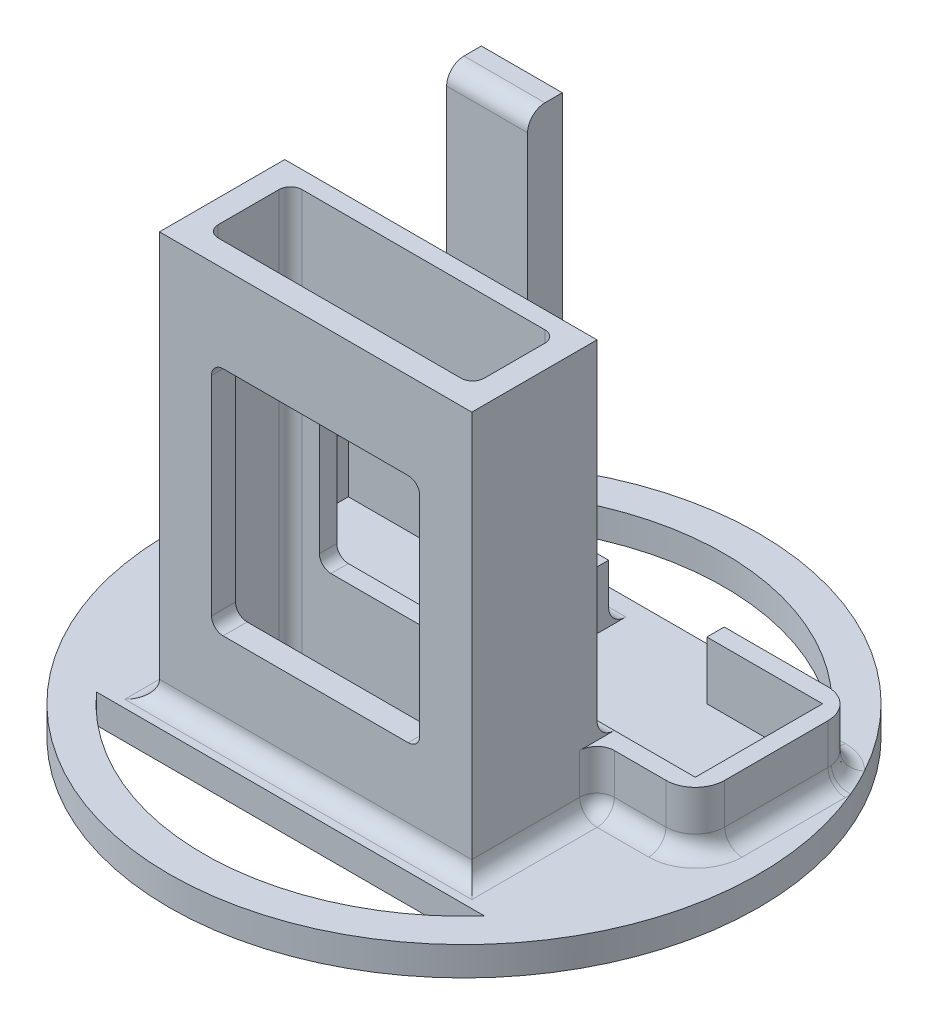
SolidWorks part; units mm, degrees
ref_plane "Front Plane" through (0, 0, 0) normal (0, 0, 1) x (1, 0, 0)
ref_plane "Top Plane" through (0, 0, 0) normal (0, 1, 0) x (1, 0, 0)
ref_plane "Right Plane" through (0, 0, 0) normal (1, 0, 0) x (0, 0, -1)
sketch "Sketch1" plane through (0, 0, 0) normal (0, 1, 0) x (1, 0, 0)
  line L1 (-16.7705, 15) -> (16.7705, 15)
  line L2 (-16.7705, 15) -> (-16.7705, -15)
  line L3 (-16.7705, -15) -> (16.7705, -15)
  line L4 (16.7705, 15) -> (16.7705, -15)
  line L5 (-16.7705, 15) -> (16.7705, -15) construction
  line L6 (-16.7705, -15) -> (16.7705, 15) construction
  circle A0 centre (0, 0) radius 25.5
  circle A1 centre (0, 0) radius 22.5
  dimension "D1" = 51
  dimension "D2" = 45
  dimension "D3" = 30
extrude "Boss-Extrude1" add sketch "Sketch1" along normal blind 2.5 contours L2 A1 | L4 A1 | L4 L1 L2 L3 | A0 A1 region at (0, 0, 0) region at (-19.0893, 0, 0) region at (19.0893, 0, 0) region at (-24.7788, 0, 0)
sketch "Sketch2" plane through (0, 2.5, 0) normal (0, 1, 0) x (1, 0, 0)
  line L1 (-20.5, 5.5) -> (20.5, 5.5)
  line L2 (-20.5, 5.5) -> (-20.5, -5.5)
  line L3 (-20.5, -5.5) -> (20.5, -5.5)
  line L4 (20.5, 5.5) -> (20.5, -5.5)
  line L5 (-20.5, 5.5) -> (20.5, -5.5) construction
  line L6 (-20.5, -5.5) -> (20.5, 5.5) construction
  line L7 (-20.5, -0.5) -> (20.5, -0.5)
  line L8 (-20.5, -0.5) -> (-20.5, 10.5)
  line L9 (-20.5, 10.5) -> (20.5, 10.5)
  line L10 (20.5, -0.5) -> (20.5, 10.5)
  line L11 (-20.5, -0.5) -> (-22, -0.5)
  line L12 (-20.5, -0.5) -> (-20.5, 10.5)
  line L13 (-20.5, 10.5) -> (-22, 10.5)
  line L14 (-22, -0.5) -> (-22, 10.5)
  line L15 (-22, -0.5) -> (20.5, -0.5)
  line L16 (-22, -0.5) -> (-22, -2)
  line L17 (-22, -2) -> (20.5, -2)
  line L18 (20.5, -0.5) -> (20.5, -2)
  line L19 (-22, 10.5) -> (20.5, 10.5)
  line L20 (-22, 10.5) -> (-22, 12)
  line L21 (-22, 12) -> (20.5, 12)
  line L22 (20.5, 10.5) -> (20.5, 12)
  line L23 (20.5, -2) -> (22, -2)
  line L24 (20.5, -2) -> (20.5, 12)
  line L25 (20.5, 12) -> (22, 12)
  line L26 (22, -2) -> (22, 12)
  point P0 (0, 0)
  dimension "D1" = 41
  dimension "D2" = 11
  dimension "D3" = 41
  dimension "D4" = 5
  dimension "D5" = 11
  dimension "D6" = 1.5
  dimension "D7" = 11
  dimension "D8" = 1.5
  dimension "D9" = 42.5
  dimension "D10" = 1.5
  dimension "D11" = 14
  dimension "D12" = 1.5
extrude "Boss-Extrude2" add sketch "Sketch2" along normal blind 5 contours L14 L11 L2 L8 L13 | L16 L17 L2 L11 | L2 L17 L4 L7 | L23 L26 L25 L22 L10 L4 | L9 L22 L21 L20 L13 region at (-21.25, 2.5, -5) region at (21.25, 2.5, -5) region at (0, 2.5, 1.25) region at (-21.25, 2.5, 1.25) region at (-0.75, 2.5, -11.25)
fillet "Fillet1" radius 2.54 4 edges at (-22, 5, 2) (22, 5, 2) (22, 5, -12) (-22, 5, -12)
sketch "Sketch3" plane through (0, 7.5, 0) normal (0, 1, 0) x (1, 0, 0)
  line L0 (-19.46, 12) -> (19.46, 12) construction
  line L1 (20.5, 10.5) -> (10.5, 10.5)
  line L2 (20.5, 10.5) -> (20.5, 12)
  line L3 (20.5, 12) -> (10.5, 12)
  line L4 (10.5, 10.5) -> (10.5, 12)
  line L5 (-20.5, 10.5) -> (20.5, 10.5) construction
  line L6 (10.5, 12) -> (0.5, 12)
  line L7 (10.5, 12) -> (10.5, 10.5)
  line L8 (10.5, 10.5) -> (0.5, 10.5)
  line L9 (0.5, 12) -> (0.5, 10.5)
  line M9 (-20.5, 10.5) -> (20.5, 10.5)
  line M16 (19.46, 12) -> (-19.46, 12)
  dimension "D1" = 10
  dimension "D2" = 10
extrude "Cut-Extrude1" cut sketch "Sketch3" against normal blind 5 contours L9 L4 M16 M9 region at (5.5, 7.5, -11.25)
sketch "Sketch4" plane through (0, 2.5, 0) normal (0, 1, 0) x (1, 0, 0)
  line L0 (-16.7705, 15) -> (16.7705, 15) construction
  line L1 (-20.5, 10.5) -> (-13.5, 10.5)
  line L2 (-20.5, 10.5) -> (-20.5, 12)
  line L3 (-20.5, 12) -> (-13.5, 12)
  line L4 (-13.5, 10.5) -> (-13.5, 12)
  line L5 (-13.5, 12) -> (-6.5, 12)
  line L6 (-13.5, 12) -> (-13.5, 15)
  line L7 (-13.5, 15) -> (-6.5, 15)
  line L8 (-6.5, 12) -> (-6.5, 15)
  line M9 (-19.46, 12) -> (0.5, 12)
  line M24 (16.7705, 15) -> (-16.7705, 15)
  dimension "D1" = 7
  dimension "D2" = 1.5
  dimension "D3" = 7
extrude "Boss-Extrude3" add sketch "Sketch4" along normal blind 35 contours L8 L6 M9 M24 region at (-10, 2.5, -13.5)
fillet "Fillet2" radius 1.5 12 edges at (-3, 2.5, -12) (-16.48, 2.5, -12) (21.2561, 2.5, -11.2561) (22, 2.5, -5) (21.2561, 2.5, 1.2561) (0, 2.5, 2) (-21.2561, 2.5, 1.2561) (-22, 2.5, -5) (-21.2561, 2.5, -11.2561) (-6.5, 2.5, -13.5) (-13.5, 2.5, -13.5) (-10, 7.5, -12)
fillet "Fillet3" radius 1.5 1 edges at (-10, 37.5, -12)
sketch "Sketch5" plane through (0, 2.5, 0) normal (0, 1, 0) x (1, 0, 0)
  line L0 (0, 0) -> (0, -6.5)
  line L1 (-19.46, -2) -> (19.46, -2) construction
  line L2 (-11.5, -2.25) -> (11.5, -2.25)
  line L3 (-11.5, -2.25) -> (-11.5, -10.75)
  line L4 (-11.5, -10.75) -> (11.5, -10.75)
  line L5 (11.5, -2.25) -> (11.5, -10.75)
  line L6 (-11.5, -2.25) -> (11.5, -10.75) construction
  line L7 (-11.5, -10.75) -> (11.5, -2.25) construction
  line L8 (-11.5, -10.75) -> (-13.5, -10.75)
  line L9 (-11.5, -10.75) -> (-11.5, -2)
  line L10 (-11.5, -2) -> (-13.5, -2)
  line L11 (-13.5, -10.75) -> (-13.5, -2)
  line L12 (19.46, -3.5) -> (-19.46, -3.5) construction
  line L13 (-13.5, -10.75) -> (13.5, -10.75)
  line L14 (-13.5, -10.75) -> (-13.5, -12.8255)
  line L15 (-13.5, -12.8255) -> (13.5, -12.8255)
  line L16 (13.5, -10.75) -> (13.5, -12.8255)
  line L17 (11.5, -10.75) -> (13.5, -10.75)
  line L18 (11.5, -10.75) -> (11.5, -2)
  line L19 (11.5, -2) -> (13.5, -2)
  line L20 (13.5, -10.75) -> (13.5, -2)
  line L21 (-13.5, -2) -> (13.5, -2)
  line L22 (-13.5, -2) -> (-13.5, -3.5)
  line L23 (-13.5, -3.5) -> (13.5, -3.5)
  line L24 (13.5, -2) -> (13.5, -3.5)
  line L25 (-11.5, -2) -> (11.5, -2)
  line M20 (19.46, -3.5) -> (-19.46, -3.5)
  dimension "D1" = 23
  dimension "D2" = 8.5
  dimension "D3" = 6.5
  dimension "D4" = 2
  dimension "D5" = 27
extrude "Boss-Extrude5" add sketch "Sketch5" along normal blind 35 contours L21 L9 L2 L0 | L2 L3 L0 M20 | L5 L2 L0 M20 | L21 L0 L2 L18 | L20 L19 L18 L5 M20 | L13 L20 L5 M20 | L16 L13 L4 L8 L14 L15 | L11 L8 L3 M20 | L11 L3 L9 L10 M20 region at (5.75, 2.5, 2.125) region at (-5.75, 2.5, 2.125) region at (5.75, 2.5, 2.875) region at (-5.75, 2.5, 2.875) region at (-12.5, 2.5, 2.75) region at (12.5, 2.5, 2.75) region at (-12.5, 2.5, 7.125) region at (12.5, 2.5, 7.125) region at (0, 2.5, 11.7878)
fillet "Fillet4" radius 1.5 1 edges at (0, 7.5, 2)
fillet "Fillet5" radius 1.5 7 edges at (-13.5, 5.75, 2) (-13.5, 2.9393, 2.4393) (13.5, 5.75, 2) (13.5, 2.9393, 2.4393) (0, 2.5, 12.8255) (-13.5, 2.5, 8.1628) (13.5, 2.5, 8.1628)
fillet "Fillet6" radius 1 4 edges at (11.5, 20, 10.75) (11.5, 20, 3.5) (-11.5, 20, 10.75) (-11.5, 20, 3.5)
sketch "Sketch6" plane through (0, 0, 12.8255) normal (0, 0, 1) x (1, 0, 0)
  line L1 (-13.5, 37.5) -> (0, 37.5)
  line L2 (-13.5, 37.5) -> (-13.5, 20)
  line L3 (-13.5, 20) -> (0, 20)
  line L4 (0, 37.5) -> (0, 20)
  line L5 (-9, 30) -> (9, 30)
  line L6 (-9, 30) -> (-9, 10)
  line L7 (-9, 10) -> (9, 10)
  line L8 (9, 30) -> (9, 10)
  line L9 (-9, 30) -> (9, 10) construction
  line L10 (-9, 10) -> (9, 30) construction
  dimension "D1" = 13.5
  dimension "D2" = 17.5
  dimension "D3" = 18
  dimension "D4" = 20
extrude "Cut-Extrude3" cut sketch "Sketch6" against normal blind 19.76 contours L5 L6 L3 L4 | L8 L5 L4 L3 L6 L7 region at (1.5, 18.3333, 12.8255) region at (-4.5, 25, 12.8255)
fillet "Fillet7" radius 1 8 edges at (9, 30, 11.7878) (9, 30, 2.75) (-9, 30, 2.75) (-9, 30, 11.7878) (9, 10, 2.75) (-9, 10, 2.75) (-9, 10, 11.7878) (9, 10, 11.7878)
